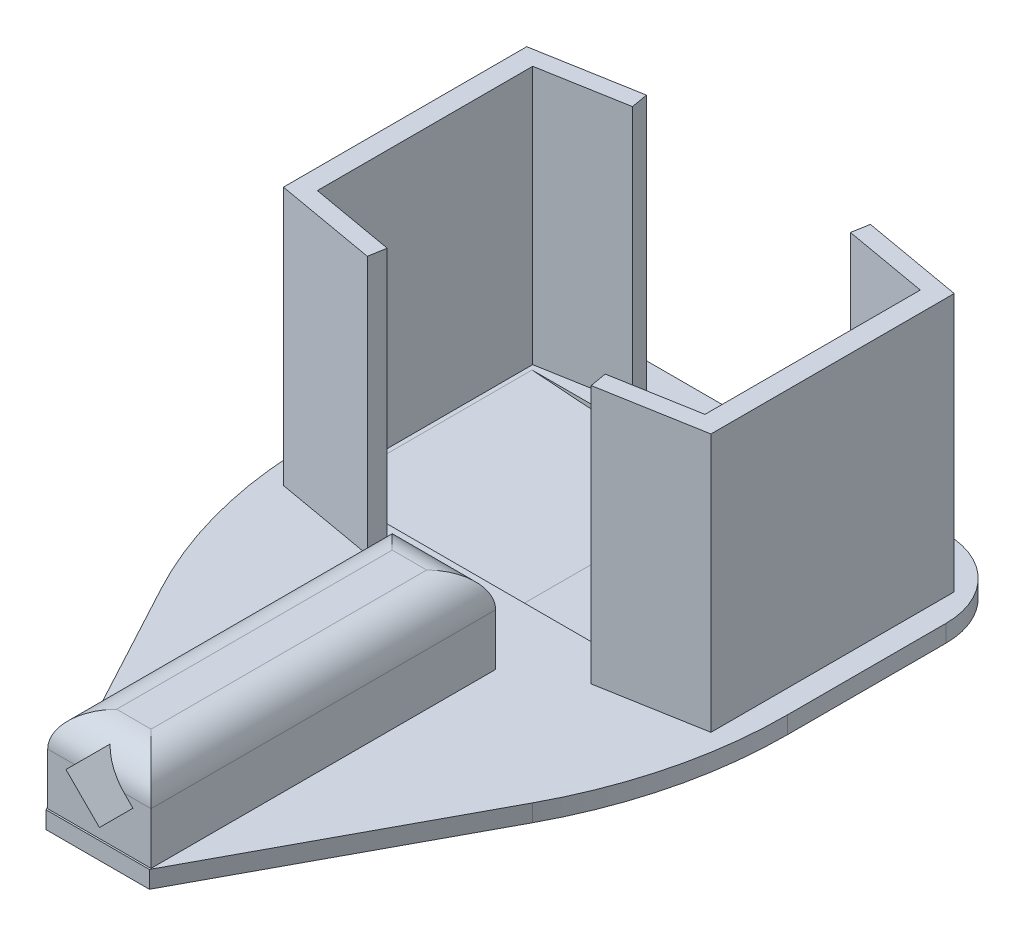
SolidWorks part; units mm, degrees
ref_plane "Front Plane" through (0, 0, 0) normal (0, 0, 1) x (1, 0, 0)
ref_plane "Top Plane" through (0, 0, 0) normal (0, 1, 0) x (1, 0, 0)
ref_plane "Right Plane" through (0, 0, 0) normal (1, 0, 0) x (0, 0, -1)
sketch "Sketch1" plane through (0, 0, 0) normal (0, 1, 0) x (1, 0, 0)
  line L0 (-6, -38.9038) -> (6, -38.9038)
  line L1 (-27.5, -38.9038) -> (27.5, -38.9038)
  line L2 (-27.5, -38.9038) -> (-27.5, 41.0962)
  line L3 (-27.5, 41.0962) -> (27.5, 41.0962)
  line L4 (27.5, -38.9038) -> (27.5, 41.0962)
  line L5 (6, -38.9038) -> (27.5, 1.0962)
  line L6 (-6, -38.9038) -> (-27.5, 1.0962)
  point P0 (0, 21.0962)
  point P7 (0, -38.9038)
  dimension "D1" = 55
  dimension "D2" = 80
  dimension "D3" = 12
extrude "Boss-Extrude1" add sketch "Sketch1" along normal blind 2 contours L6 L0 L5 L4 L3 L2 region at (0, 0, -7.5746)
sketch "Sketch2" plane through (0, 2, 0) normal (0, 1, 0) x (1, 0, 0)
  line L0 (0, 21.6017) -> (0, 34.1017)
  line L1 (-22.5, 21.6017) -> (22.5, 21.6017)
  line L2 (22.5, 9.1017) -> (22.5, 34.1017)
  line L3 (22.5, 34.1017) -> (12.6519, 35.8381)
  line L4 (12.6519, 35.8381) -> (12.9992, 37.8078)
  line L5 (12.9992, 37.8078) -> (24.8169, 35.724)
  line L6 (24.8169, 35.724) -> (24.8169, 7.4793)
  line L7 (22.5, 9.1017) -> (12.6519, 7.3652)
  line L8 (12.6519, 7.3652) -> (12.9992, 5.3956)
  line L9 (12.9992, 5.3956) -> (24.8169, 7.4793)
  line L10 (-12.6519, 7.3652) -> (-12.9992, 5.3956)
  line L11 (-12.9992, 5.3956) -> (-24.8169, 7.4793)
  line L12 (-22.5, 9.1017) -> (-12.6519, 7.3652)
  line L13 (-24.8169, 35.724) -> (-24.8169, 7.4793)
  line L14 (-22.5, 9.1017) -> (-22.5, 34.1017)
  line L15 (-12.9992, 37.8078) -> (-24.8169, 35.724)
  line L16 (-12.6519, 35.8381) -> (-12.9992, 37.8078)
  line L17 (-22.5, 34.1017) -> (-12.6519, 35.8381)
  point P5 (0, 34.1017)
  point P6 (0, 21.6017)
  point P9 (22.5, 21.6017)
  point P16 (24.8169, 21.6017)
  dimension "D1" = 12.5
  dimension "D2" = 45
  dimension "D3" = 10
  dimension "D4" = 90
  dimension "D5" = 2
  dimension "D6" = 12
extrude "Boss-Extrude2" add sketch "Sketch2" along normal blind 30 contours L14 L17 L16 L15 L13 L11 L10 L12 | L8 L9 L6 L5 L4 L3 L2 L7 region at (22.8462, 2, -27.8517) region at (-22.8462, 2, -15.3517)
sketch "Sketch3" plane through (0, 2, 0) normal (0, 1, 0) x (1, 0, 0)
  line L1 (-6.0055, -38.7) -> (5.9945, -38.7)
  line L2 (-6.0055, -38.7) -> (-6.0055, 1.3)
  line L3 (-6.0055, 1.3) -> (5.9945, 1.3)
  line L4 (5.9945, -38.7) -> (5.9945, 1.3)
  line L5 (-6.0055, -38.7) -> (5.9945, 1.3) construction
  line L6 (-6.0055, 1.3) -> (5.9945, -38.7) construction
  point P0 (-0.0055, -18.7)
  dimension "D1" = 40
  dimension "D2" = 12
  dimension "D3" = 18.7
extrude "Boss-Extrude3" add sketch "Sketch3" along normal blind 10
sketch "Sketch4" plane through (0, 0, 38.7) normal (0, 0, 1) x (1, 0, 0)
  line L0 (0, 0) -> (0, 7)
  line L2 (0, 3.1109) -> (3.8891, 7)
  line L3 (0, 3.1109) -> (-3.8891, 7)
  line L4 (-3.8891, 7) -> (0, 10.8891)
  line L5 (3.8891, 7) -> (0, 10.8891)
  line L6 (0, 3.1109) -> (0, 10.8891) construction
  line L7 (-3.8891, 7) -> (3.8891, 7) construction
  dimension "D1" = 5.5
  dimension "D2" = 5.5
  dimension "D3" = 7
extrude "Cut-Extrude1" cut sketch "Sketch4" against normal blind 35 contours L2 L5 L4 L3 region at (-1.8668, 5.1332, 38.7)
sketch "Sketch6" plane through (0, 2, 0) normal (0, 1, 0) x (1, 0, 0)
  line L1 (-22, 33.5266) -> (22, 33.5266)
  line L2 (-22, 33.5266) -> (-22, 9.6446)
  line L3 (-22, 9.6446) -> (22, 9.6446)
  line L4 (22, 33.5266) -> (22, 9.6446)
  line L5 (-22, 33.5266) -> (22, 9.6446) construction
  line L6 (-22, 9.6446) -> (22, 33.5266) construction
  point P0 (0, 21.5856)
  point P5 (0, 0)
  dimension "D1" = 44
extrude "Cut-Extrude2" cut sketch "Sketch6" against normal blind 1
fillet "Fillet1" radius 280 2 edges at (22, 1, -21.5856) (-22, 1, -21.5856)
fillet "Fillet2" radius 9 2 edges at (27.5, 1, -41.0962) (-27.5, 1, -41.0962)
fillet "Fillet3" radius 4 4 edges at (-0.0055, 12, -1.3) (-6.0055, 12, 18.7) (5.9945, 12, 18.7) (-0.0055, 12, 38.7)
fillet "Fillet4" radius 50 2 edges at (-27.5, 1, -1.0962) (27.5, 1, -1.0962)
